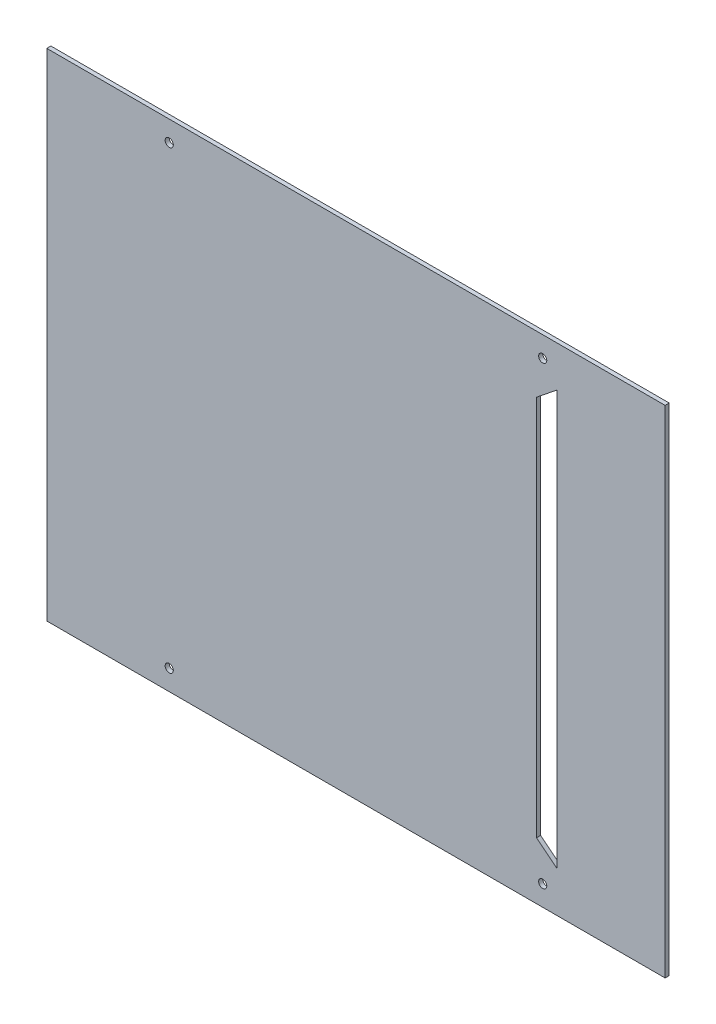
SolidWorks part; units mm, degrees
ref_plane "Front Plane" through (0, 0, 0) normal (0, 0, 1) x (1, 0, 0)
ref_plane "Top Plane" through (0, 0, 0) normal (0, 1, 0) x (1, 0, 0)
ref_plane "Right Plane" through (0, 0, 0) normal (1, 0, 0) x (0, 0, -1)
sketch "Sketch1" plane through (0, 0, 0) normal (0, 0, 1) x (1, 0, 0)
  line L0 (0, 0) -> (-206.9982, 0) construction
  line L1 (151.5, -121.5) -> (-151.5, -121.5)
  line L2 (151.5, -121.5) -> (151.5, 121.5)
  line L3 (151.5, 121.5) -> (-151.5, 121.5)
  line L4 (-151.5, -121.5) -> (-151.5, 121.5)
  line L5 (151.5, -121.5) -> (-151.5, 121.5) construction
  line L6 (151.5, 121.5) -> (-151.5, -121.5) construction
  line L7 (139.0309, -111.5) -> (-139.0309, -111.5) construction
  line L8 (139.0309, -111.5) -> (139.0309, 111.5) construction
  line L9 (139.0309, 111.5) -> (-139.0309, 111.5) construction
  line L10 (-139.0309, -111.5) -> (-139.0309, 111.5) construction
  line L11 (139.0309, -111.5) -> (-139.0309, 111.5) construction
  line L12 (139.0309, 111.5) -> (-139.0309, -111.5) construction
  line L13 (98.5, 101.5) -> (98.5, -101.5)
  line L14 (88.5, 93.4802) -> (88.5, -93.4802)
  line L15 (98.5, 101.5) -> (88.5, 93.4802)
  line L16 (98.5, -101.5) -> (88.5, -93.4802)
  circle A0 centre (-91.5, 111.5) radius 2
  circle A1 centre (91.5, 111.5) radius 2
  circle A2 centre (91.5, -111.5) radius 2
  circle A3 centre (-91.5, -111.5) radius 2
  point P0 (0, 0)
  point P5 (0, 0)
  dimension "D4" = 4
  dimension "D5" = 4
  dimension "D1" = 303
  dimension "D2" = 243
  dimension "D3" = 10
  dimension "D6" = 60
  dimension "D7" = 60
  dimension "D8" = 53
  dimension "D9" = 10
  dimension "D10" = 10
  dimension "D11" = 10
extrude "Boss-Extrude1" add sketch "Sketch1" along normal blind 2
